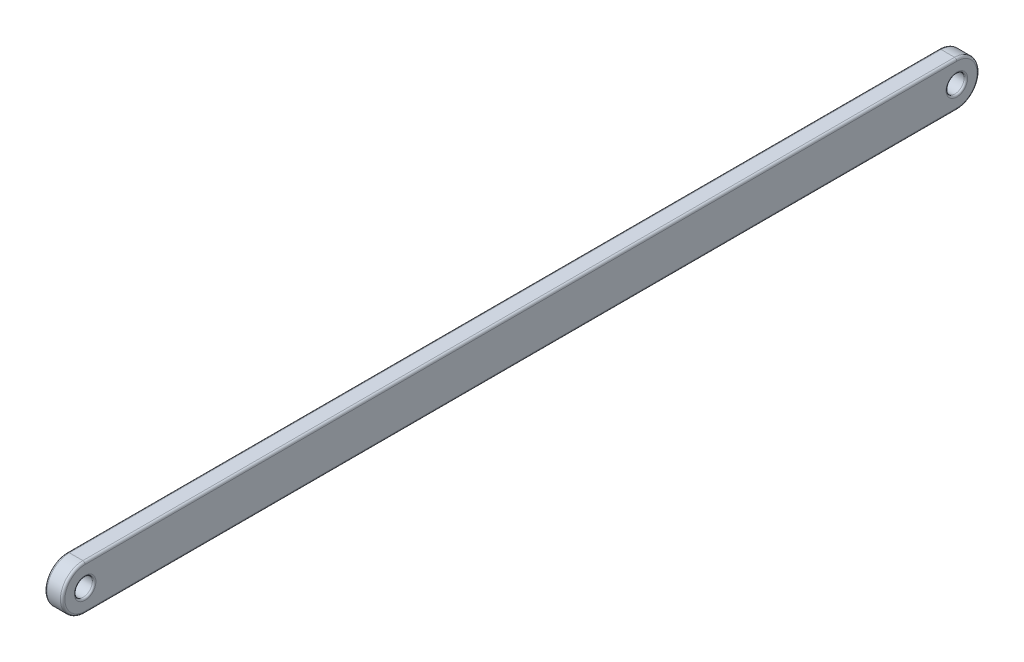
SolidWorks part; units mm, degrees
ref_plane "Front Plane" through (0, 0, 0) normal (0, 0, 1) x (1, 0, 0)
ref_plane "Top Plane" through (0, 0, 0) normal (0, 1, 0) x (1, 0, 0)
ref_plane "Right Plane" through (0, 0, 0) normal (1, 0, 0) x (0, 0, -1)
sketch "Sketch1" plane through (0, 0, 0) normal (1, 0, 0) x (0, 0, -1)
  line L1 (0, 0) -> (48.5, 0)
  line L3 (0, -2.5) -> (48.5, -2.5)
  line L8 (0, 0) -> (0, -2.5) construction
  line L12 (48.5, 0) -> (48.5, -2.5) construction
  circle A0 centre (0, -1.25) radius 0.5
  arc A1 (0, -2.5) -> (0, 0) centre (0, -1.25) cw
  circle A2 centre (48.5, -1.25) radius 0.5
  arc A3 (48.5, 0) -> (48.5, -2.5) centre (48.5, -1.25) cw
  point P1 (48.5, 0)
  point P3 (0, 0)
  point P5 (0, 0)
  point P7 (-1, 0)
  point P9 (0, 0)
  point P12 (47.4354, -2.5)
  point P13 (47.4765, 0)
  point P15 (0, 0)
  dimension "D1" = 1
  dimension "D4" = 1
  dimension "D5" = 48.5
  dimension "D6" = 2.5
extrude "Boss-Extrude1" add sketch "Sketch1" along normal blind 1
fillet "Fillet1" radius 0.125 8 edges at (1, -2.5, -24.25) (0, -2.5, -24.25) (0, 0, -24.25) (1, 0, -24.25) (0, -1.25, -49.75) (1, -1.25, -49.75) (0, -1.25, 1.25) (1, -1.25, 1.25)
fillet "Fillet2" radius 0.1 4 edges at (0, -1.25, -0.5) (1, -1.25, -0.5) (0, -1.25, -49) (1, -1.25, -49)
